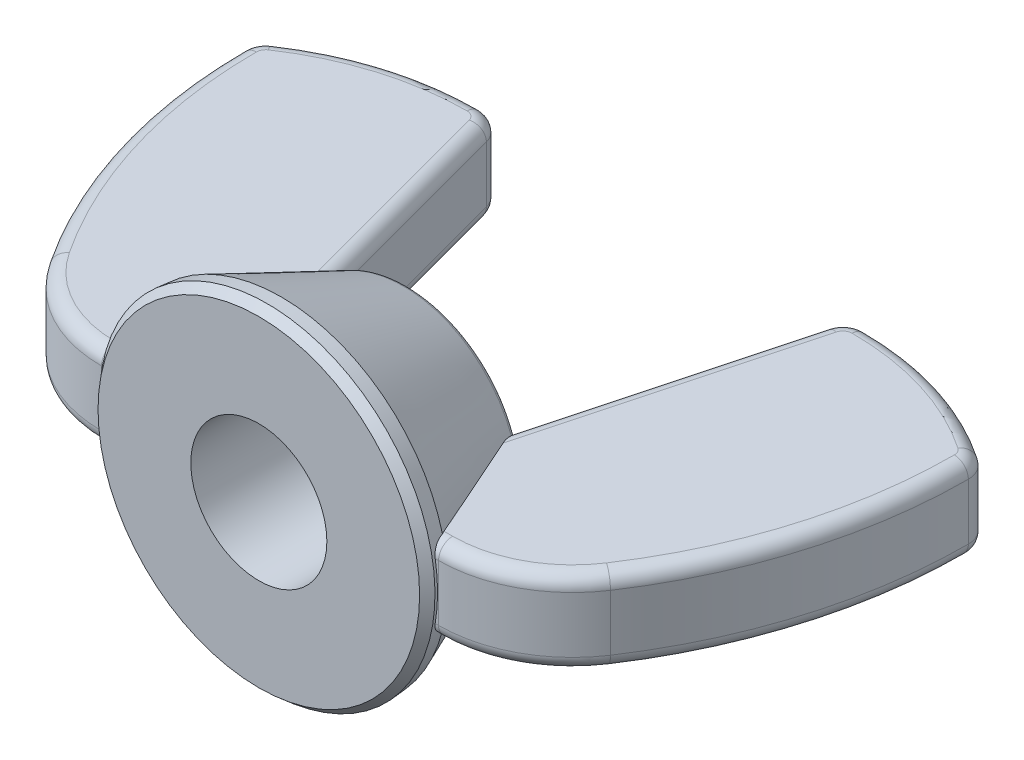
SolidWorks part; units mm, degrees
material "AISI 304"
ref_plane "Front Plane" through (0, 0, 0) normal (0, 0, 1) x (1, 0, 0)
ref_plane "Top Plane" through (0, 0, 0) normal (0, 1, 0) x (1, 0, 0)
ref_plane "Right Plane" through (0, 0, 0) normal (1, 0, 0) x (0, 0, -1)
sketch "Sketch1" plane through (0, 0, 0) normal (0, 0, 1) x (1, 0, 0)
  circle A0 centre (0, 0) radius 2.0828
  circle A1 centre (0, 0) radius 5.1594
  dimension "D1" = 10.3187
sketch "Sketch2" plane through (0, 0, 0) normal (0, 1, 0) x (1, 0, 0)
  line L0 (0, 0) -> (0, 12.7) construction
  line L1 (-2.0828, 0) -> (2.0828, 0) construction
  line L2 (-11.1125, 12.7) -> (11.1125, 12.7) construction
  line L3 (11.1125, 12.7) -> (11.1125, 0) construction
  line L4 (-11.1125, 12.7) -> (-11.1125, 0) construction
  line L5 (-11.1125, 0) -> (11.1125, 0) construction
  line L6 (-3.5186, 4.572) -> (3.5186, 4.572) construction
  line L7 (0, 0) -> (0, 4.572) construction
  line L8 (-4.3144, 0.6858) -> (5.1594, 0.6858) construction
  line L9 (5.1594, 0) -> (5.1594, 4.572) construction
  line L10 (3.1667, 4.572) -> (5.3943, 12.8856)
  line L12 (3.5186, 4.572) -> (3.5186, 0.3429) construction
  line L13 (-5.1594, 0) -> (5.1594, 0) construction
  line L14 (5.1594, 0.6858) -> (3.5186, 4.572) construction
  line L15 (5.3943, 12.8856) -> (11.3449, 11.0664)
  line L16 (11.3449, 11.0664) -> (7.152, 0.3429)
  line L17 (5.1594, 0.3429) -> (7.152, 0.3429)
  line L19 (3.1667, 0.3429) -> (5.1594, 0.3429)
  line L20 (-3.1667, 4.572) -> (3.1667, 4.572) construction
  line L21 (3.1667, 4.572) -> (3.1667, 0.3429)
  circle A3 centre (10.3959, 10.6072) radius 0.7166 construction
  circle A4 centre (5.8945, 11.9834) radius 0.7166 construction
  dimension "D6" = 1.4332
  dimension "D2" = 4.572
  dimension "D4" = 7.0371
  dimension "D1" = 0.6858
  dimension "D3" = 22.89
  dimension "D5" = 0.3429
  dimension "D8" = 17
  dimension "D9" = 6.3334
  dimension "D7" = 15
sketch "Sketch13" plane through (0, 0, 0) normal (0, 1, 0) x (1, 0, 0)
  line L1 (3.1667, 4.572) -> (3.1667, 0.3429) construction
  line L2 (3.1667, 4.572) -> (5.3943, 12.8856) construction
  line L3 (-11.1125, 12.7) -> (11.1125, 12.7) construction
  line L4 (11.1125, 12.7) -> (11.1125, 0) construction
  line L5 (5.1594, 0.3429) -> (7.152, 0.3429) construction
  line L6 (3.1667, 0.3429) -> (5.1594, 0.3429) construction
  line L7 (0, 0) -> (0, 4.572) construction
  line L8 (-2.0828, 0) -> (2.0828, 0) construction
  line L9 (0, 0) -> (0, 12.7) construction
  line L10 (-3.5186, 4.572) -> (3.5186, 4.572) construction
  line L11 (3.1667, 0.3429) -> (5.1594, 0.3429)
  line L12 (3.1667, 4.572) -> (3.1667, 0.3429)
  line L13 (3.1667, 4.572) -> (5.2023, 12.1689)
  circle A0 centre (10.3959, 10.6072) radius 0.7166 construction
  circle A1 centre (5.8945, 11.9834) radius 0.7166 construction
  arc A5 (11.1125, 10.6072) -> (10.7966, 11.2013) centre (10.3959, 10.6072) ccw
  arc A6 (5.8945, 12.7) -> (5.2023, 12.1689) centre (5.8945, 11.9834) ccw
  arc A7 (8.5807, 2.183) -> (11.1125, 10.6072) centre (-4.1686, 10.6072) ccw
  arc A8 (10.7966, 11.2013) -> (5.8945, 12.7) centre (5.8945, 3.9335) ccw
  arc A10 (5.1594, 0.3429) -> (8.5807, 2.183) centre (5.1594, 4.4437) ccw
extrude "Extrude2" add sketch "Sketch13" along normal mid plane 2.5797
sketch "Sketch3" plane through (0, 0, 0) normal (0, 0, 1) x (1, 0, 0)
  circle A0 centre (0, 0) radius 5.1594 construction
  circle A1 centre (0, 0) radius 5.1594
extrude "Extrude1" add sketch "Sketch3" against normal up to vertex (0.6858 mm away) draft 5 separate body up to point (5.1594, 0, -0.6858)
sketch "Sketch15" plane through (0, 0, -0.6858) normal (0, 0, -1) x (-1, 0, 0)
  circle A1 centre (0, 0) radius 5.0994
  circle A2 centre (0, 0) radius 5.0994
  dimension "D1" = 0
extrude "Extrude3" add sketch "Sketch15" along normal up to vertex (3.8862 mm away) draft 22.89 up to point (0, 0, -4.572)
fillet "Fillet3" radius 0.254 1 edges at (-3.4586, 0, -4.572)
sketch "Sketch12" plane through (0, 0, -4.572) normal (0, 0, -1) x (-1, 0, 0)
  circle A1 centre (0, 0) radius 5.0994
  circle A2 centre (0, 0) radius 5.0994 construction
  dimension "D1" = 10.1988
sketch "Sketch4" plane through (0, 0, 0) normal (0, 0, 1) x (1, 0, 0)
  circle A0 centre (0, 0) radius 2.0828 construction
  circle A1 centre (0, 0) radius 2.0828
extrude "Cut-Extrude1" cut sketch "Sketch4" against normal through all
sketch "Sketch5" plane through (0, 0, 0) normal (0, 0, 1) x (1, 0, 0)
  circle A0 centre (0, 0) radius 2.0828 construction
  circle A1 centre (0, 0) radius 2.0828
curve "Helix/Spiral1" pitch 0.7937 height 7.747 turns 9.76 parameters "pitch"=0.7937
sketch "Sketch6" plane through (0, 0, 0) normal (0, 1, 0) x (1, 0, 0)
  line L0 (-2.0828, -0.6945) -> (-1.5672, -0.3969)
  line L1 (-1.5672, -0.3969) -> (-1.5672, -0.2977)
  line L2 (-1.5672, -0.2977) -> (-2.0828, 0)
  line L3 (-2.0828, -0.6945) -> (-2.0828, 0)
  line L4 (-2.0828, -0.3473) -> (-1.5672, -0.3473) construction
  line L5 (-1.825, -0.5457) -> (-1.825, -0.1488) construction
  line L6 (-2.0828, 0) -> (2.0828, 0) construction
  dimension "D1" = 60
  dimension "D2" = 0.0992
  dimension "D3" = 0.3969
sweep "Sweep1" [suppressed] add profiles "Sketch6" path "Helix/Spiral1"
sketch "Sketch7" plane through (0, 0, 0) normal (0, 0, 1) x (1, 0, 0)
  circle A1 centre (0, 0) radius 5.1594
  circle A2 centre (0, 0) radius 5.1594
  dimension "D1" = 0
extrude "Cut-Extrude2" [suppressed] cut sketch "Sketch7" along normal through all
ref_plane "Plane1" through (0, 0, -4.572) normal (0, 0, 1) x (1, 0, 0)
sketch "Sketch8" plane through (0, 0, -4.572) normal (0, 0, 1) x (1, 0, 0)
  circle A0 centre (0, 0) radius 5.0994 construction
  circle A2 centre (0, 0) radius 5.0994
extrude "Cut-Extrude3" [suppressed] cut sketch "Sketch8" against normal through all
sketch "Sketch9" plane through (0, 0, 0) normal (0, 0, 1) x (1, 0, 0)
  circle A1 centre (0, 0) radius 2.0828
  circle A2 centre (0, 0) radius 2.0828
  dimension "D1" = 0
extrude "Cut-Extrude4" [suppressed] cut sketch "Sketch9" against normal through all draft 45
sketch "Sketch11" plane through (0, 0, -4.572) normal (0, 0, 1) x (1, 0, 0)
  circle A0 centre (0, 0) radius 2.0828 construction
  circle A1 centre (0, 0) radius 2.032
  circle A2 centre (0, 0) radius 2.0828 construction
  dimension "D1" = 0.0508
extrude "Cut-Extrude5" [suppressed] cut sketch "Sketch11" along normal through all draft 45
chamfer "Chamfer1" distance 0.2572 angle 45 1 edges at (5.1594, 0, 0) first distance on face at (-5.0994, 0, -0.6858)
fillet "Fillet4" radius 0.4299 14 edges at (4.163, 1.2898, -0.3429) (7.1018, 1.2898, -0.8321) (5.4582, 1.2898, -12.5519) (8.4575, 1.2898, -12.3169) (11.0286, 1.2898, -10.9436) (4.163, -1.2898, -0.3429) (7.1018, -1.2898, -0.8321) (5.4582, -1.2898, -12.5519) (8.4575, -1.2898, -12.3169) (11.0286, -1.2898, -10.9436) (10.4659, 1.2898, -6.209) (10.4659, -1.2898, -6.209) (4.1845, 1.2898, -8.3704) (4.1845, -1.2898, -8.3704)
mirror "Mirror6" about plane through (0, 0, 0) normal (1, 0, 0) of bodies 108 113
combine bodies "Combine2" operation type add bodies to combine 116 108 102
equation "\"D1@Sketch1\" = \"thread dia@Sketch1\"*1.725"
equation "\"D2@Sketch2\" = \"B@Sketch2\"*.36"
equation "\"D3@Helix/Spiral1\" = \"D2@Sketch2\"+.125"
equation "\"D2@Sketch6\" = \"pitch@Helix/Spiral1\"*.125"
equation "\"D3@Sketch6\" = \"pitch@Helix/Spiral1\"*.5"
equation "\"D4@Sketch2\" = \"D1@Sketch12\"*.69"
equation "\"D1@Extrude2\" = \"D1@Sketch1\"*.25"
equation "\"D1@Sketch2\" = \"D2@Sketch2\"*.150"
equation "\"D5@Sketch2\" = \"D1@Sketch2\"/2"
equation "\"D3@Extrude3\" = \"D3@Sketch2\""
equation "\"D1@Chamfer1\" = \"D5@Sketch2\"*.75"
equation "\"D9@Sketch2\" = \"D4@Sketch2\"*.9"
equation "\"D6@Sketch2\" = \"D1@Extrude2\"/1.8"
equation "\"D1@Fillet4\" = \"D1@Extrude2\"/6"
